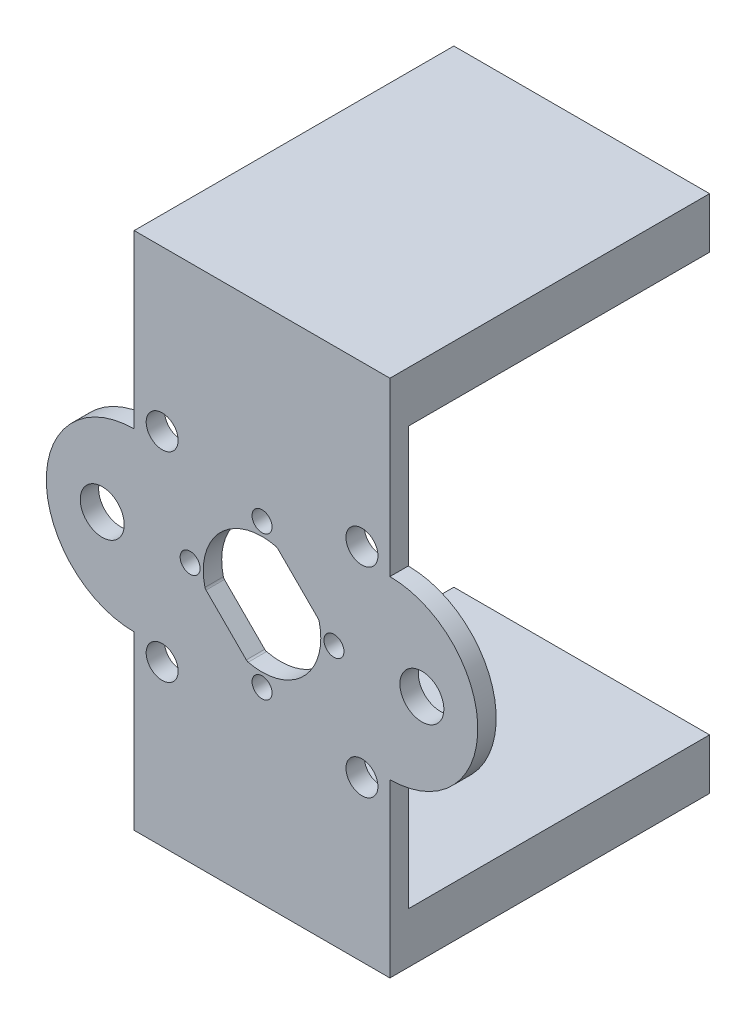
SolidWorks part; units mm, degrees
ref_plane "Front Plane" through (0, 0, 0) normal (0, 0, 1) x (1, 0, 0)
ref_plane "Top Plane" through (0, 0, 0) normal (0, 1, 0) x (1, 0, 0)
ref_plane "Right Plane" through (0, 0, 0) normal (1, 0, 0) x (0, 0, -1)
sketch "Sketch1" plane through (0, 0, 0) normal (0, 0, 1) x (1, 0, 0)
  line L1 (-16, -32.5) -> (16, -32.5)
  line L2 (-16, -32.5) -> (-16, 32.5)
  line L3 (-16, 32.5) -> (16, 32.5)
  line L4 (16, -32.5) -> (16, 32.5)
  line L5 (-16, -32.5) -> (16, 32.5) construction
  line L6 (-16, 32.5) -> (16, -32.5) construction
  point P0 (0, 0)
  dimension "D1" = 32
  dimension "D2" = 65
extrude "Boss-Extrude1" add sketch "Sketch1" against normal blind 40
sketch "Sketch2" plane through (0, 0, -40) normal (0, 0, -1) x (-1, 0, 0)
  line L0 (16, 32.5) -> (16, -32.5) construction
  line L1 (-16, -26.15) -> (16, -26.15)
  line L2 (-16, -26.15) -> (-16, 26.15)
  line L3 (-16, 26.15) -> (16, 26.15)
  line L4 (16, -26.15) -> (16, 26.15)
  line L5 (-16, -26.15) -> (16, 26.15) construction
  line L6 (-16, 26.15) -> (16, -26.15) construction
  point P0 (0, 0)
  dimension "D1" = 52.3
extrude "Cut-Extrude1" cut sketch "Sketch2" against normal blind 37.7
sketch "Sketch3" plane through (0, 0, 0) normal (0, 0, 1) x (1, 0, 0)
  line L0 (16, -32.5) -> (-16, -32.5)
  line L1 (-16, -11) -> (-16, -32.5)
  line L2 (16, -32.5) -> (16, -11)
  line L3 (-16, 32.5) -> (16, 32.5)
  line L4 (-16, 32.5) -> (-16, 11)
  line L5 (16, 11) -> (16, 32.5)
  line L6 (-7.01, -1.9702) -> (-1.9702, -7.01)
  line L7 (7.01, 1.9702) -> (1.9702, 7.01)
  line L8 (0, 32.5) -> (0, -32.5) construction
  circle A0 centre (12.5, -12.5) radius 2
  circle A1 centre (-12.5, -12.5) radius 2
  circle A2 centre (20, 0) radius 5
  circle A3 centre (-20, 0) radius 5
  circle A4 centre (-12.5, 12.5) radius 2
  arc A5 (16, -11) -> (16, 11) centre (16, 0) ccw
  arc A6 (-16, 11) -> (-16, -11) centre (-16, 0) ccw
  circle A7 centre (12.5, 12.5) radius 2
  arc A8 (7.1424, 1.7347) -> (7.01, 1.9702) centre (6.6565, 1.6167) ccw
  arc A9 (-1.9702, -7.01) -> (-1.7347, -7.1424) centre (-1.6167, -6.6565) ccw
  arc A10 (-7.1424, -1.7347) -> (-7.01, -1.9702) centre (-6.6565, -1.6167) ccw
  circle A11 centre (0, -9) radius 1.25
  circle A12 centre (9, 0) radius 1.25
  arc A13 (-1.7347, -7.1424) -> (7.1424, 1.7347) centre (0, 0) ccw
  circle A14 centre (-9, 0) radius 1.25
  arc A15 (1.7347, 7.1424) -> (-7.1424, -1.7347) centre (0, 0) ccw
  circle A16 centre (0, 9) radius 1.25
  arc A17 (-22.75, 0) -> (-17.25, 0) centre (-20, 0) ccw
  arc A18 (-17.25, 0) -> (-22.75, 0) centre (-20, 0) ccw
  arc A19 (17.25, 0) -> (22.75, 0) centre (20, 0) ccw
  arc A20 (22.75, 0) -> (17.25, 0) centre (20, 0) ccw
  spline S0 degree 1 poles (1.9702, 7.01) (1.7347, 7.1424) knots 0 0 1 1
  point P46 (27, 0)
  point P47 (-27, 0)
  dimension "D3" = 32.5
  dimension "D4" = 20
  dimension "D5" = 20
  dimension "D6" = 20
  dimension "D7" = 20
  dimension "D8" = 25
  dimension "D9" = 25
  dimension "D10" = 9
  dimension "D11" = 9
  dimension "D12" = 9
  dimension "D13" = 9
  dimension "D14" = 20
  dimension "D15" = 20
extrude "Boss-Extrude4" add sketch "Sketch3" against normal blind 2.3 contours A6 L1 L0 L2 A5 L5 L3 L4
extrude "Cut-Extrude3" cut sketch "Sketch3<7>" against normal blind 2.3 contours A17 A18 | A19 A20 | A4 | L8 A15 A10 L6 A9 A13 | A12 | L8 A11 | A11 L8 | A14 | L8 A16 | A16 L8 | A7 | A1 | A0 | A15 L8 A13 A8 L7 S0 region at (-0.5305, -9, 0) region at (0.5305, -9, 0) region at (-3.0156, 0.2996, 0) region at (3.0156, -0.2999, 0) region at (0.5305, 9, 0) region at (-0.5305, 9, 0) region at (12.5, -12.5, 0) region at (-12.5, -12.5, 0) region at (-12.5, 12.5, 0) region at (12.5, 12.5, 0) region at (9, 0, 0) region at (-9, 0, 0) region at (-20, 0, 0) region at (20, 0, 0)
sketch "Sketch3<7>" plane through (0, 0, 0) normal (0, 0, 1) x (1, 0, 0) same geometry as "Sketch3"
